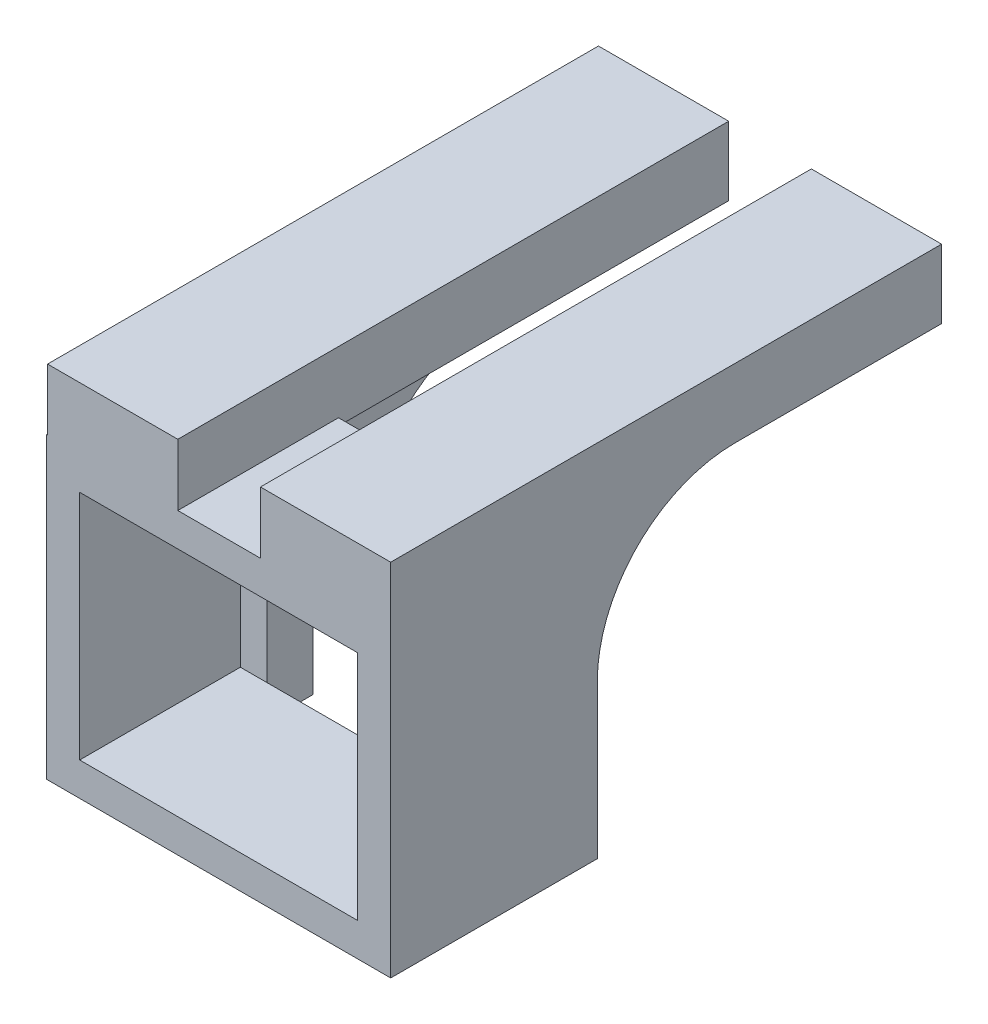
SolidWorks part; units mm, degrees
ref_plane "Front Plane" through (0, 0, 0) normal (0, 0, 1) x (1, 0, 0)
ref_plane "Top Plane" through (0, 0, 0) normal (0, 1, 0) x (1, 0, 0)
ref_plane "Right Plane" through (0, 0, 0) normal (1, 0, 0) x (0, 0, -1)
sketch "Sketch1" plane through (0, 0, 0) normal (0, 0, 1) x (1, 0, 0)
  line L0 (2.7055, 9.5331) -> (13.9855, 9.5331) construction
  line L1 (2.7055, 9.5331) -> (2.7055, 2.7413) construction
  line L3 (-3.3445, 4.4831) -> (8.7555, 4.4831)
  line L4 (-3.3445, 4.4831) -> (-3.3445, 14.5831)
  line L5 (-3.3445, 14.5831) -> (8.7555, 14.5831)
  line L6 (8.7555, 4.4831) -> (8.7555, 14.5831)
  line L7 (-3.3445, 4.4831) -> (8.7555, 14.5831) construction
  line L8 (-3.3445, 14.5831) -> (8.7555, 4.4831) construction
  line L9 (-4.7945, 16.0331) -> (10.2055, 16.0331)
  line L10 (-4.7945, 16.0331) -> (-4.7945, 3.0331)
  line L11 (-4.7945, 3.0331) -> (10.2055, 3.0331)
  line L12 (10.2055, 16.0331) -> (10.2055, 3.0331)
  line L13 (-4.7945, 16.0331) -> (10.2055, 3.0331) construction
  line L14 (-4.7945, 3.0331) -> (10.2055, 16.0331) construction
  dimension "D1" = 10.1
  dimension "D2" = 12.1
  dimension "D3" = 13
  dimension "D4" = 15
extrude "Boss-Extrude1" add sketch "Sketch1" along normal blind 7 contours L10 L9 L12 L11 | L4 L3 L6 L5
sketch "Sketch2" plane through (0, 0, 0) normal (0, 0, -1) x (-1, 0, 0)
  line L0 (-4.5306, 18.7826) -> (-4.5306, 15.6605) construction
  line L1 (-4.5306, 17.2216) -> (5.9382, 17.2216) construction
  line L2 (-4.5306, 15.7216) -> (-4.5306, 18.7216)
  line L3 (-4.4806, 18.7716) -> (-4.4806, 15.6716) construction
  line L5 (-2.7306, 18.7716) -> (-2.7306, 16.4124) construction
  line L6 (-0.9306, 15.7216) -> (-0.9306, 18.7216)
  line L7 (-4.5306, 18.7216) -> (-10.2055, 18.7216)
  line L8 (-10.2055, 15.7216) -> (-10.2055, 18.7216)
  line L10 (-4.5306, 15.7216) -> (-10.2055, 15.7216)
  line L12 (-0.9306, 15.7216) -> (4.7443, 15.7216)
  line L13 (4.7443, 15.7216) -> (4.7443, 18.7216)
  line L14 (-0.9306, 18.7216) -> (4.7443, 18.7216)
  line L15 (-10.2055, 16.0331) -> (-10.2055, 3.0331) construction
  line L16 (-4.4806, 18.7716) -> (-6.2306, 18.7716) construction
  point P7 (-4.5306, 17.2216)
  dimension "D1" = 3
  dimension "D2" = 0.05
  dimension "D3" = 0.1
extrude "Boss-Extrude2" add sketch "Sketch2" along normal blind 17 and the other way blind 7
sketch "Sketch3" plane through (0, 0, 0) normal (0, 0, -1) x (-1, 0, 0)
  line L0 (-10.2055, 15.7216) -> (-5.4306, 15.7216)
  line L1 (-10.2055, 18.7216) -> (-10.2055, 15.7216) construction
  line L2 (-10.2055, 15.7216) -> (-10.2055, 3.0331) construction
  line L3 (-10.2055, 15.7216) -> (-4.5306, 15.7216) construction
  line L4 (-5.4306, 15.7216) -> (-5.4306, 13.7235)
  line L5 (-10.2055, 15.7216) -> (-10.2055, 13.7235)
  line L7 (-5.2306, 15.6716) -> (-5.2306, 13.5544) construction
  line L8 (-2.7306, 18.7716) -> (-2.7306, 16.0331) construction
  line L9 (-0.9306, 16.0331) -> (-4.5306, 16.0331) construction
  line L11 (4.7443, 15.7216) -> (4.7443, 13.7235)
  line L12 (-0.0306, 15.7216) -> (-0.0306, 13.7235)
  line L13 (4.7443, 15.7216) -> (-0.0306, 15.7216)
  line L14 (-10.2055, 13.7235) -> (-10.2055, 9.6216)
  line L17 (4.7443, 13.7235) -> (4.7443, 9.6216)
  line L18 (-7.6414, 9.6216) -> (-7.6414, 3.0331)
  line L19 (4.7945, 3.0331) -> (-10.2055, 3.0331) construction
  line L20 (-7.6414, 3.0331) -> (-10.2055, 3.0331)
  line L21 (-10.2055, 3.0331) -> (-10.2055, 9.6216)
  line L22 (2.1802, 9.6216) -> (2.1802, 3.0331)
  line L23 (2.1802, 3.0331) -> (4.7443, 3.0331)
  line L24 (4.7443, 3.0331) -> (4.7443, 9.6216)
  arc A0 (-5.4306, 13.7235) -> (-7.6414, 9.6216) centre (-2.7306, 9.6216) ccw
  arc A1 (-0.0306, 13.7235) -> (2.1802, 9.6216) centre (-2.7306, 9.6216) cw
  dimension "D1" = 0.2
extrude "Boss-Extrude3" add sketch "Sketch3" along normal blind 2
fillet "Fillet1" radius 6 2 edges at (-2.3568, 15.7216, -2) (7.818, 15.7216, -2)
